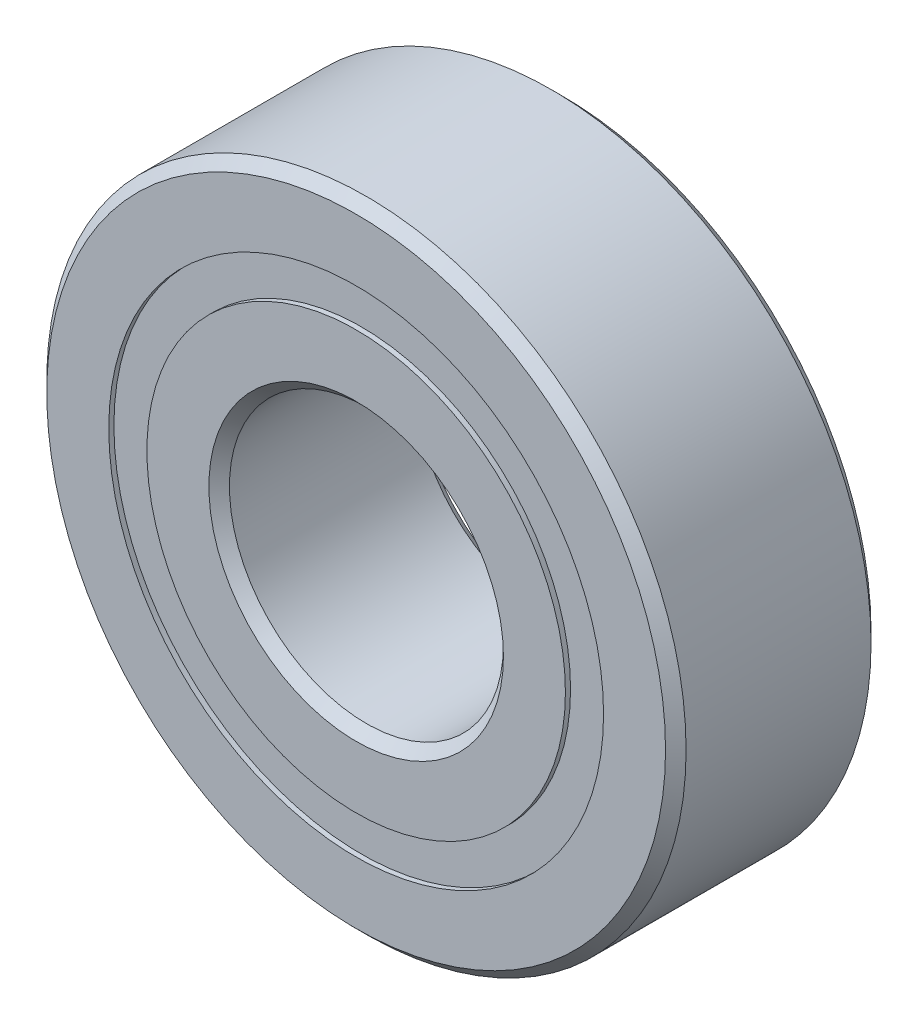
SolidWorks part; units mm, degrees
ref_plane "Front Plane" through (0, 0, 0) normal (0, 0, 1) x (1, 0, 0)
ref_plane "Top Plane" through (0, 0, 0) normal (0, 1, 0) x (1, 0, 0)
ref_plane "Right Plane" through (0, 0, 0) normal (1, 0, 0) x (0, 0, -1)
sketch "Sketch1" plane through (0, 0, 0) normal (1, 0, 0) x (0, 0, -1)
  line L0 (-3.5719, 0) -> (3.5719, 0) construction
  line L1 (0, 11.1125) -> (0, -11.1125) construction
  line L2 (3.2147, 11.1125) -> (-3.2147, 11.1125)
  line L3 (-3.2147, 11.1125) -> (-3.5719, 10.7553)
  line L4 (-3.5719, 10.7553) -> (-3.5719, 8.6004)
  line L5 (-3.5719, 8.6004) -> (-1.5875, 8.6004)
  line L6 (3.5719, 8.6004) -> (1.5875, 8.6004)
  line L7 (3.5719, 10.7553) -> (3.5719, 8.6004)
  line L8 (3.2147, 11.1125) -> (3.5719, 10.7553)
  line L9 (0, 11.1125) -> (0, 7.9375) construction
  line L10 (0, 7.9375) -> (0, 4.7625) construction
  arc A0 (-1.5875, 8.6004) -> (1.5875, 8.6004) centre (0, 7.9375) cw
  point P14 (0, 4.7625)
  dimension "Width" = 7.1437
  dimension "OD" = 22.225
  dimension "D1" = 45
  dimension "D2" = 0.3572
  dimension "Shaft Dia" = 9.525
  dimension "D3" = 3.175
  dimension "D4" = 0.6629
revolve "Revolve1" add sketch "Sketch1" angle 360 about L0
sketch "Sketch3" plane through (0, 0, 0) normal (1, 0, 0) x (0, 0, -1)
  line L0 (-3.5719, 7.2746) -> (-1.5875, 7.2746)
  line L1 (0, 11.1125) -> (0, -11.1125) construction
  line L2 (-3.5719, 10.7553) -> (-3.5719, 8.6004) construction
  line L3 (-3.5719, 7.2746) -> (-3.5719, 5.1197)
  line L4 (-3.2147, 11.1125) -> (-3.5719, 10.7553) construction
  line L5 (-3.5719, 5.1197) -> (-3.2147, 4.7625)
  line L6 (-3.2147, 4.7625) -> (3.2147, 4.7625)
  line L7 (3.2147, 11.1125) -> (3.2147, -11.1125) construction
  line L8 (3.2147, 4.7625) -> (3.5719, 5.1197)
  line L9 (3.5719, -10.7553) -> (3.5719, 10.7553) construction
  line L10 (3.5719, 5.1197) -> (3.5719, 7.2746)
  line L11 (3.5719, 7.2746) -> (1.5875, 7.2746)
  line L13 (3.2147, 11.1125) -> (3.5719, 10.7553) construction
  arc A0 (1.5875, 8.6004) -> (-1.5875, 8.6004) centre (0, 7.9375) ccw construction
  arc A1 (1.5875, 7.2746) -> (-1.5875, 7.2746) centre (0, 7.9375) cw
revolve "Revolve3" add sketch "Sketch3" angle 360 about L0
sketch "Sketch4" plane through (0, 0, 0) normal (1, 0, 0) x (0, 0, -1)
  line L0 (-1.7204, 7.9375) -> (1.7204, 7.9375)
  arc A2 (-1.7204, 7.9375) -> (1.7204, 7.9375) centre (0, 7.9375) cw
  arc A3 (1.5875, 8.6004) -> (-1.5875, 8.6004) centre (0, 7.9375) ccw construction
revolve "Revolve4" add sketch "Sketch4" angle 360 about L0
ref_axis "Axis1" through (0, 0, -3.5719) along (0, 0, 1)
pattern_circular "CirPattern1" count 10 every 36 about axis through (0, 0, -3.5719) along (0, 0, 1) of bodies 104
sketch "Sketch5" plane through (0, 0, 0) normal (1, 0, 0) x (0, 0, -1)
  line L0 (-3.5719, 8.6004) -> (-1.5875, 8.6004) construction
  line L1 (-3.3933, 8.6004) -> (-1.7204, 8.6004)
  line L2 (-3.3933, 8.6004) -> (-3.3933, 7.2746)
  line L3 (-3.3933, 7.2746) -> (-1.7204, 7.2746)
  line L4 (-1.7204, 8.6004) -> (-1.7204, 7.2746)
  line L5 (-3.5719, 7.2746) -> (-1.5875, 7.2746) construction
  line L6 (3.5719, 8.6004) -> (1.5875, 8.6004) construction
  line L7 (3.3933, 8.6004) -> (1.7204, 8.6004)
  line L8 (3.3933, 8.6004) -> (3.3933, 7.2746)
  line L9 (3.3933, 7.2746) -> (1.7204, 7.2746)
  line L10 (1.7204, 8.6004) -> (1.7204, 7.2746)
  line L11 (3.5719, 7.2746) -> (1.5875, 7.2746) construction
  line L12 (-3.2147, 11.1125) -> (-3.5719, 10.7553) construction
  point P18 (-3.3933, 10.9339)
revolve "Revolve5" add sketch "Sketch5" angle 360 about L0
equation "\"D2@Sketch1\" = \"Width@Sketch1\"*.05"
equation "\"D3@Sketch1\" = \"Width@Sketch1\"/2.25"
equation "\"D4@Sketch1\" = (((\"OD@Sketch1\"-\"Width@Sketch1\")/2)/3.25)/3.5"
equation "\"D2@CirPattern1\" = 360/\"Balls@CirPattern1\""
